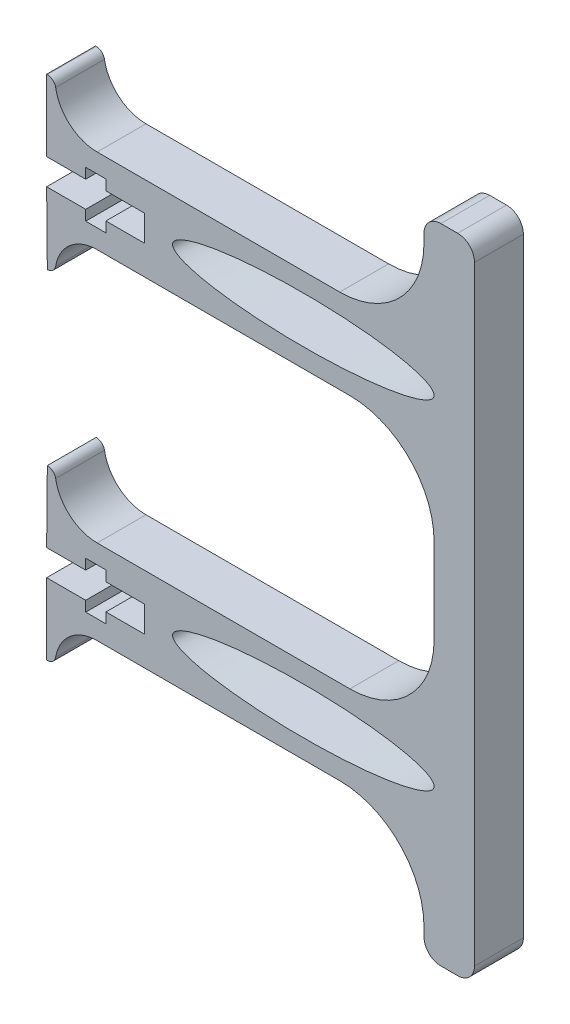
SolidWorks part; units mm, degrees
ref_plane "Front Plane" through (0, 0, 0) normal (0, 0, 1) x (1, 0, 0)
ref_plane "Top Plane" through (0, 0, 0) normal (0, 1, 0) x (1, 0, 0)
ref_plane "Right Plane" through (0, 0, 0) normal (1, 0, 0) x (0, 0, -1)
sketch "Sketch1" plane through (0, 0, 0) normal (0, 0, 1) x (1, 0, 0)
  line L0 (-12.4599, 26.5844) -> (-17.0981, 26.5844) construction
  line L1 (-12.4599, 26.5844) -> (-12.4599, 28.1323) construction
  line L2 (-12.4599, 25.0366) -> (-12.4599, 26.5844) construction
  line L3 (-11.2599, 29.3567) -> (-11.2599, 26.5844) construction
  line L4 (-5.455, 26.5844) -> (-17.0981, 26.5844) construction
  line L5 (-11.2599, 23.8122) -> (-11.2599, 26.5844) construction
  line L6 (-10.0599, 29.3567) -> (-12.4599, 29.3567)
  line L7 (-10.0599, 23.8122) -> (-12.4599, 23.8122)
  line L8 (-5.455, 25.0366) -> (-5.455, 28.1323)
  line L9 (-17.0981, 28.1323) -> (-12.4599, 28.1323)
  line L10 (-12.4599, 25.0366) -> (-17.0981, 25.0366)
  line L11 (-12.4599, 25.0366) -> (-12.4599, 23.8122)
  line L12 (-12.4599, 29.3567) -> (-12.4599, 28.1323)
  line L13 (-10.0599, 25.0366) -> (-10.0599, 23.8122)
  line L14 (-10.0599, 28.1323) -> (-5.455, 28.1323)
  line L15 (-10.0599, 25.0366) -> (-5.455, 25.0366)
  line L16 (-10.0599, 29.3567) -> (-10.0599, 28.1323)
  line L17 (-17.0981, 28.1323) -> (-17.0981, 25.0366) construction
  line L18 (-17.0981, 28.1323) -> (-17.0981, 36.6067)
  line L19 (33.7019, 26.6067) -> (33.7019, 42.6546)
  line L20 (33.7019, 26.6067) -> (33.7019, 26.5622)
  line L21 (-11.0981, 21.5622) -> (18.9019, 21.5622)
  line L22 (-17.0141, 16.5622) -> (-17.0981, 25.0366)
  line L23 (-5.455, 26.5844) -> (-3.205, 26.5844) construction
  line L24 (-17.0141, 6.4866) -> (33.7019, 6.4866) construction
  line L25 (-17.0981, 36.6067) -> (-17.0141, 36.6067)
  line L26 (-5.455, -13.6112) -> (-3.205, -13.6112) construction
  line L27 (-17.0981, -15.1591) -> (-17.0981, -12.0634) construction
  line L28 (-11.2599, -10.839) -> (-11.2599, -13.6112) construction
  line L29 (-5.455, -13.6112) -> (-17.0981, -13.6112) construction
  line L30 (-11.2599, -16.3835) -> (-11.2599, -13.6112) construction
  line L31 (-12.4599, -12.0634) -> (-12.4599, -13.6112) construction
  line L32 (-12.4599, -13.6112) -> (-12.4599, -15.1591) construction
  line L33 (-12.4599, -13.6112) -> (-17.0981, -13.6112) construction
  line L34 (-17.0981, -23.6335) -> (-17.0141, -23.6335)
  line L35 (-17.0141, -3.589) -> (-17.0981, -12.0634)
  line L36 (28.9019, 11.5622) -> (28.9019, 1.411)
  line L37 (33.7019, -13.6335) -> (33.7019, -13.589)
  line L38 (31.7019, 44.6546) -> (29.7019, 44.6546)
  line L39 (-17.0981, -15.1591) -> (-17.0981, -23.6335)
  line L40 (-10.0599, -16.3835) -> (-10.0599, -15.1591)
  line L41 (-10.0599, -12.0634) -> (-5.455, -12.0634)
  line L42 (-10.0599, -15.1591) -> (-5.455, -15.1591)
  line L43 (-10.0599, -12.0634) -> (-10.0599, -10.839)
  line L44 (-12.4599, -16.3835) -> (-12.4599, -15.1591)
  line L45 (-12.4599, -12.0634) -> (-12.4599, -10.839)
  line L46 (-12.4599, -12.0634) -> (-17.0981, -12.0634)
  line L47 (-17.0981, -15.1591) -> (-12.4599, -15.1591)
  line L48 (-5.455, -12.0634) -> (-5.455, -15.1591)
  line L49 (-10.0599, -10.839) -> (-12.4599, -10.839)
  line L50 (-10.0599, -16.3835) -> (-12.4599, -16.3835)
  line L51 (33.7019, 26.5622) -> (33.7019, -13.589)
  line L52 (18.9019, -8.589) -> (-11.0981, -8.589)
  line L53 (27.7019, 42.6546) -> (27.7019, 41.6067)
  line L54 (17.7019, 31.6067) -> (-11.0981, 31.6067)
  line L55 (27.7019, -29.6814) -> (27.7019, -28.6335)
  line L56 (33.7019, -13.6335) -> (33.7019, -29.6814)
  line L57 (31.7019, -31.6814) -> (29.7019, -31.6814)
  line L58 (17.7019, -18.6335) -> (-11.0981, -18.6335)
  line L59 (31.4519, 26.5844) -> (33.7019, 26.5844) construction
  line L60 (31.4519, -13.6112) -> (33.7019, -13.6112) construction
  arc A0 (18.9019, 21.5622) -> (28.9019, 11.5622) centre (18.9019, 11.5622) cw
  arc A1 (27.7019, 41.6067) -> (17.7019, 31.6067) centre (17.7019, 41.6067) cw
  arc A2 (-16.0281, 35.7733) -> (-11.0981, 31.6067) centre (-11.0981, 36.6067) ccw
  arc A3 (-17.0141, 36.6067) -> (-16.0281, 35.7733) centre (-17.0141, 35.6067) cw
  arc A4 (-17.0141, 16.5622) -> (-16.0281, 17.3955) centre (-17.0141, 17.5622) ccw
  arc A5 (-16.0281, 17.3955) -> (-11.0981, 21.5622) centre (-11.0981, 16.5622) cw
  arc A6 (-16.0281, -4.4223) -> (-11.0981, -8.589) centre (-11.0981, -3.589) ccw
  arc A7 (-17.0141, -3.589) -> (-16.0281, -4.4223) centre (-17.0141, -4.589) cw
  arc A8 (-17.0141, -23.6335) -> (-16.0281, -22.8001) centre (-17.0141, -22.6335) ccw
  arc A9 (-16.0281, -22.8001) -> (-11.0981, -18.6335) centre (-11.0981, -23.6335) cw
  arc A10 (33.7019, 42.6546) -> (31.7019, 44.6546) centre (31.7019, 42.6546) ccw
  arc A11 (28.9019, 1.411) -> (18.9019, -8.589) centre (18.9019, 1.411) cw
  arc A12 (29.7019, 44.6546) -> (27.7019, 42.6546) centre (29.7019, 42.6546) ccw
  arc A13 (33.7019, -29.6814) -> (31.7019, -31.6814) centre (31.7019, -29.6814) cw
  arc A14 (29.7019, -31.6814) -> (27.7019, -29.6814) centre (29.7019, -29.6814) cw
  arc A15 (27.7019, -28.6335) -> (17.7019, -18.6335) centre (17.7019, -28.6335) ccw
  ellipse E0 centre (13.3775, 26.5844) end of major axis (28.9019, 26.5844) minor radius 2.7722
  ellipse E1 centre (13.3775, -13.6112) end of major axis (28.9019, -13.6112) minor radius 2.7722
  point P39 (-16.0981, 36.6067)
  point P87 (-16.0981, -23.6335)
  dimension "D6" = 10
  dimension "D11" = 1
  dimension "D4" = 10
  dimension "D7" = 10
  dimension "D12" = 2
  dimension "D1" = 2.4
  dimension "D2" = 1.2244
  dimension "D3" = 4.6382
  dimension "D5" = 50.8
  dimension "D8" = 2
  dimension "D9" = 18.55
  dimension "D10" = 1
  dimension "D13" = 30
extrude "Boss-Extrude1" add sketch "Sketch1" along normal blind 5.8
